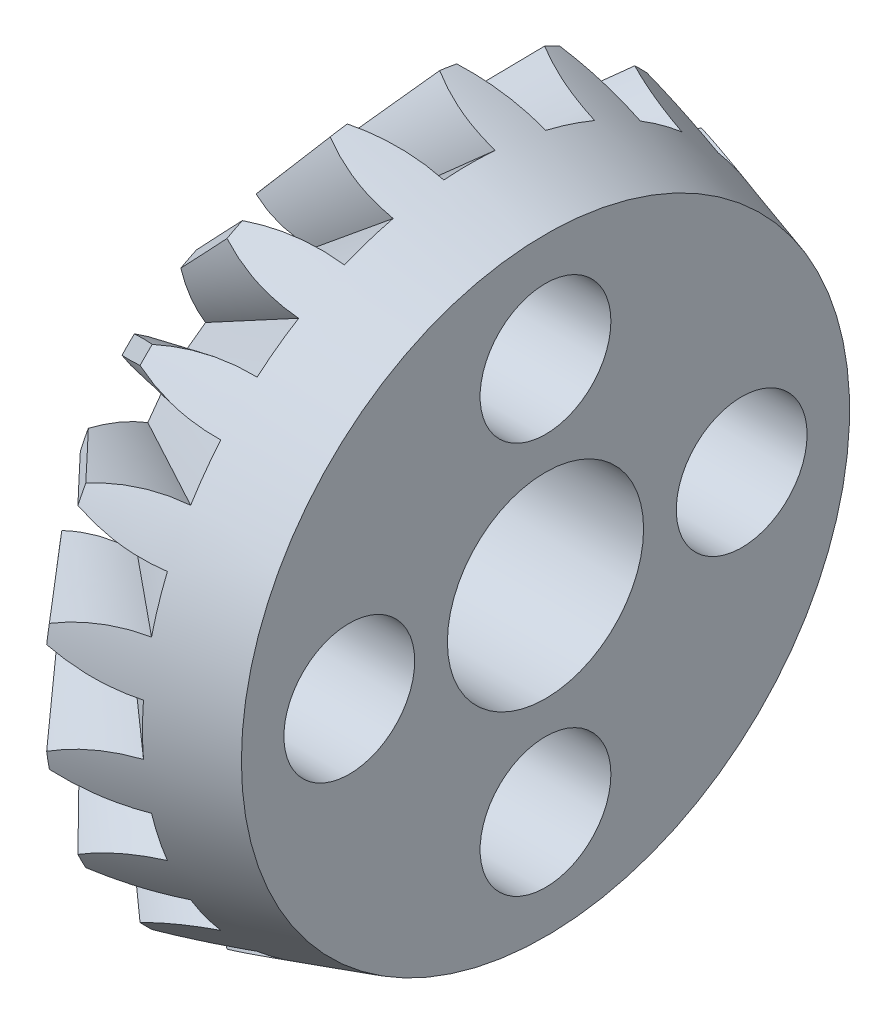
SolidWorks part; units mm, degrees
ref_plane "Front" through (0, 0, 0) normal (0, 0, 1) x (1, 0, 0)
ref_plane "Top" through (0, 0, 0) normal (0, 1, 0) x (1, 0, 0)
ref_plane "Right" through (0, 0, 0) normal (1, 0, 0) x (0, 0, -1)
sketch "Sketch1" plane through (0, 0, 0) normal (0, 0, 1) x (1, 0, 0)
  line L0 (0, 0) -> (14.6, 0) construction
  line L1 (0, 3) -> (14.6, 3)
  line L2 (14.6, 3) -> (14.6, 8)
  line L3 (14.6, 8) -> (7.6, 8)
  line L4 (7.6, 8) -> (7.6, 9.3)
  line L5 (7.6, 9.3) -> (2.9515, 10.7)
  line L6 (2.9515, 10.7) -> (0, 7.3031)
  line L7 (0, 7.3031) -> (0, 3)
  line L8 (5.2757, 10) -> (0, 3.9281) construction
  dimension "D1" = 49.013
  dimension "Overall Length" = 14.6
  dimension "OD" = 21.4
  dimension "For Shaft" = 6
  dimension "Face Width" = 4.5
  dimension "Hub Dia" = 16
  dimension "Hub Width" = 7
  dimension "PD" = 20
revolve "Revolve1" add sketch "Sketch1" angle 360 about L0
sketch "Sketch2" plane through (0, 0, 0) normal (-1, 0, 0) x (0, 0, 1)
  circle A0 centre (0, 0) radius 10
  dimension "Pitch Dia" = 20
sketch "Sketch3" plane through (0, 0, 0) normal (-1, 0, 0) x (0, 0, 1)
  line L0 (-10, 0) -> (10, 0) construction
  point P2 (0, 0)
  dimension "teeth" = 20
sketch "Sketch5" plane through (0, 0, 0) normal (-1, 0, 0) x (0, 0, 1)
  line L0 (0, 0) -> (0, 10.7) construction
  line L1 (0, 0) -> (0.8395, 10.667) construction
  line L2 (0, 0) -> (-0.8395, 10.667) construction
  line L4 (-10, 0) -> (10, 0) construction
  line L5 (-0.4198, 5.3335) -> (0.4198, 5.3335)
  line L6 (0, 0) -> (-3.3065, 10.1763) construction
  line L7 (0, 0) -> (3.3065, 10.1763) construction
  circle A0 centre (0, 0) radius 10.7 construction
  arc A1 (-0.4198, 5.3335) -> (-3.3065, 10.1763) centre (-6.7627, 4.8343) ccw
  arc A2 (0.4198, 5.3335) -> (3.3065, 10.1763) centre (6.7627, 4.8343) cw
  arc A3 (-3.3065, 10.1763) -> (3.3065, 10.1763) centre (0, 0) cw
  point P10 (0, 0)
  dimension "D1" = 9
  dimension "D2" = 36
ref_plane "Plane1" through (5.2757, 0, 0) normal (1, 0, 0) x (0, 0, -1)
sketch "Sketch6" plane through (5.2757, 0, 0) normal (1, 0, 0) x (0, 0, -1)
  line L0 (0, 0) -> (0, 16.05) construction
  line L1 (0, 0) -> (0.8395, 10.667) construction
  line L2 (0, 0) -> (-0.8395, 10.667) construction
  line L3 (0, 0) -> (5.215, 16.05) construction
  line L4 (0, 0) -> (-5.215, 16.05) construction
  line L5 (5.215, 16.05) -> (-5.215, 16.05) construction
  line L6 (0, 10.7) -> (0, 0) construction
  line L7 (-5.215, 16.05) -> (5.215, 16.05)
  circle A0 centre (0, 0) radius 10.7 construction
  arc A1 (-0.7846, 9.9692) -> (-5.215, 16.05) centre (-7.9465, 9.4055) ccw
  arc A2 (0.7846, 9.9692) -> (5.215, 16.05) centre (7.9465, 9.4055) cw
  circle A3 centre (0, 0) radius 10 construction
  arc A4 (0.7846, 9.9692) -> (-0.7846, 9.9692) centre (0, 0) ccw
  dimension "D1" = 9
  dimension "D2" = 36
  dimension "D3" = 16.05
  dimension "D4" = 10.7
loft "Cut-Loft1" cut profiles "Sketch6", "Sketch5" connector at (5.2757, 16.05, -5.215) connector at (0, 10.1763, -3.3065)
pattern_circular "CirPattern1" count 20 over 360 about axis through (0, 0, 0) along (-1, 0, 0) of "Cut-Loft1"
sketch "Sketch7" plane through (0, 0, 0) normal (-1, 0, 0) x (0, 0, 1)
  circle A0 centre (0, 0) radius 10
sketch "Sketch8" plane through (0, 0, 0) normal (0, 1, 0) x (1, 0, 0)
  line L0 (-6.4, 21) -> (-6.4, 6.4) construction
  line L2 (14.6, -8) -> (14.6, 8) construction
  line B0 (-13.6503, 6.4) -> (-17.0063, 9.3515) construction
  line B1 (-17.0063, 9.3515) -> (-15.7, 14) construction
  line B2 (-15.7, 14) -> (-14.4, 14) construction
  line B3 (-14.4, 14) -> (-14.4, 21) construction
  line B4 (-14.4, 21) -> (1.6, 21) construction
  line B5 (1.6, 21) -> (1.6, 14) construction
  line B6 (1.6, 14) -> (2.9, 14) construction
  line B7 (2.9, 14) -> (4.2063, 9.3515) construction
  line B8 (4.2063, 9.3515) -> (0.8503, 6.4) construction
  line B9 (0.8503, 6.4) -> (-13.6503, 6.4) construction
  dimension "D1" = 21
  dimension "D2" = 21
sketch_block_instance "Block2-1"
sketch_block "Block2"
sketch "草图1" plane through (14.6, 0, 0) normal (1, 0, 0) x (0, 0, -1)
  circle A0 centre (0, 0) radius 3
  circle A1 centre (0, 0) radius 8
extrude "切除-拉伸1" cut sketch "草图1" against normal blind 7
sketch "草图2" plane through (7.6, 0, 0) normal (1, 0, 0) x (0, 0, -1)
  circle A0 centre (0, 0) radius 6 construction
  circle A1 centre (0, 6) radius 2
  circle A2 centre (-6, 0) radius 2
  circle A3 centre (0, -6) radius 2
  circle A4 centre (6, 0) radius 2
  dimension "D1" = 4
  dimension "D2" = 4
  dimension "D3" = 4
  dimension "D4" = 4
extrude "切除-拉伸2" cut sketch "草图2" against normal through all
ref_plane "基准面1" through (-6.4, 0, 0) normal (1, 0, 0) x (0, 0, -1)
ref_axis "基准轴1" through (7.6, 0, 0) along (-1, 0, 0)
ref_point "点2"
equation "\"D1@Sketch5\"=(360deg/20)/2"
equation "\"D2@Sketch5\"=(360deg/20)/.5"
equation "\"D1@Sketch6\"=(360deg/\"teeth@Sketch5\")/2"
equation "\"D2@Sketch6\"=(360deg/\"teeth@Sketch5\")/.5"
equation "\"D3@Sketch6\"=\"D4@Sketch6\"*1.5"
